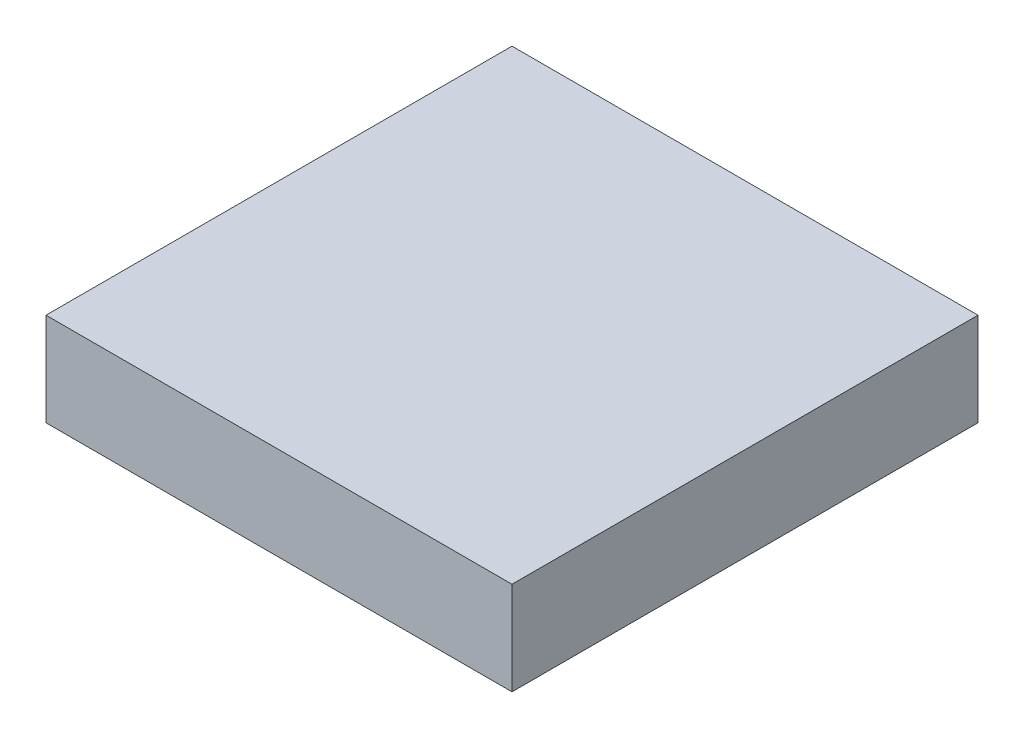
SolidWorks part; units mm, degrees
ref_plane "Front Plane" through (0, 0, 0) normal (0, 0, 1) x (1, 0, 0)
ref_plane "Top Plane" through (0, 0, 0) normal (0, 1, 0) x (1, 0, 0)
ref_plane "Right Plane" through (0, 0, 0) normal (1, 0, 0) x (0, 0, -1)
sketch "Sketch1" plane through (0, 0, 0) normal (0, 1, 0) x (1, 0, 0)
  line L1 (-63.5, 63.5) -> (63.5, 63.5)
  line L2 (-63.5, 63.5) -> (-63.5, -63.5)
  line L3 (-63.5, -63.5) -> (63.5, -63.5)
  line L4 (63.5, 63.5) -> (63.5, -63.5)
  line L5 (-63.5, 63.5) -> (63.5, -63.5) construction
  line L6 (-63.5, -63.5) -> (63.5, 63.5) construction
  point P0 (0, 0)
  dimension "D1" = 127
  dimension "D2" = 127
extrude "Boss-Extrude1" add sketch "Sketch1" along normal blind 25.4
